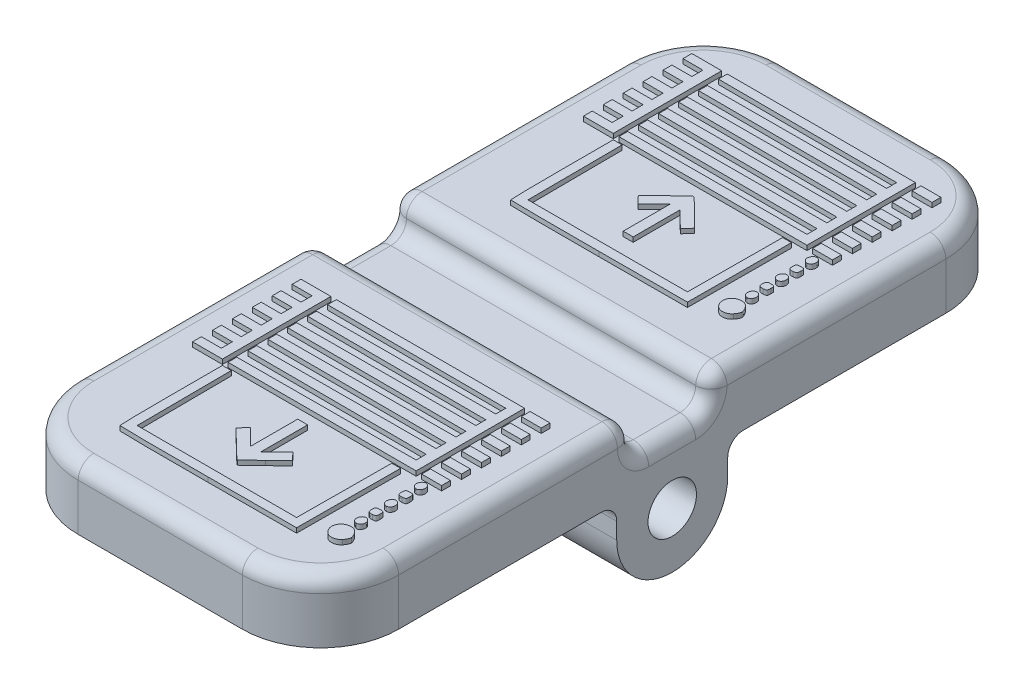
SolidWorks part; units mm, degrees
other "Camera1"
ref_plane "Front Plane" through (0, 0, 0) normal (0, 0, 1) x (1, 0, 0)
ref_plane "Top Plane" through (0, 0, 0) normal (0, 1, 0) x (1, 0, 0)
ref_plane "Right Plane" through (0, 0, 0) normal (1, 0, 0) x (0, 0, -1)
sketch "Sketch1" plane through (0, 0, 0) normal (0, 1, 0) x (1, 0, 0)
  line L1 (0, 0) -> (20.5, 0)
  line L2 (0, 0) -> (0, 45)
  line L3 (0, 45) -> (20.5, 45)
  line L4 (20.5, 0) -> (20.5, 45)
  dimension "D1" = 20.5
  dimension "D2" = 45
extrude "Boss-Extrude1" add sketch "Sketch1" along normal blind 2.5
sketch "Sketch2" plane through (0, 2.5, 0) normal (0, 1, 0) x (1, 0, 0)
  line L0 (20.5, 0) -> (20.5, 45) construction
  line L1 (0, 45) -> (20.5, 45)
  line L2 (0, 45) -> (0, 25)
  line L3 (0, 25) -> (20.5, 25)
  line L4 (20.5, 45) -> (20.5, 25)
  line L7 (0, 0) -> (20.5, 0)
  line L8 (0, 0) -> (0, 20)
  line L9 (0, 20) -> (20.5, 20)
  line L10 (20.5, 0) -> (20.5, 20)
  dimension "D1" = 20
  dimension "D2" = 20
extrude "Boss-Extrude2" add sketch "Sketch2" along normal blind 2
fillet "Fillet1" radius 1 16 edges at (0, 2.5, -22.5) (20.5, 2.5, -22.5) (10.25, 2.5, -20) (0, 4.5, -10) (10.25, 4.5, 0) (20.5, 4.5, -10) (10.25, 4.5, -20) (10.25, 2.5, -25) (10.25, 4.5, -25) (20.5, 4.5, -35) (10.25, 4.5, -45) (0, 4.5, -35) (0, 3.5, -20) (20.5, 3.5, -20) (20.5, 3.5, -25) (0, 3.5, -25)
fillet "Fillet2" radius 5 8 edges at (0.2929, 4.2071, -44.7071) (20.2071, 4.2071, -44.7071) (20.2071, 4.2071, -0.2929) (0.2929, 4.2071, -0.2929) (0, 1.75, 0) (20.5, 1.75, 0) (20.5, 1.75, -45) (0, 1.75, -45)
sketch "Sketch4" plane through (0, 0, 0) normal (-1, 0, 0) x (0, 0, 1)
  line L0 (-26.05, -1.55) -> (-26.05, 1.5)
  line L1 (-40, 0) -> (-5, 0) construction
  line L2 (-26.05, 1.5) -> (-18.95, 1.5)
  line L3 (-18.95, 1.5) -> (-18.95, -1.55)
  line L4 (-21, 1.5) -> (-24, 1.5) construction
  circle A0 centre (-22.5, -1.55) radius 1.55
  arc A1 (-26.05, -1.55) -> (-18.95, -1.55) centre (-22.5, -1.55) ccw
  circle A2 centre (-22.5, -1.55) radius 3.55 construction
  point P4 (-22.5, 0)
  dimension "D1" = 3.1
  dimension "D2" = 2
extrude "Boss-Extrude3" add sketch "Sketch4" against normal up to surface (20.5 mm away) up to face at (20.5, 2.0214, -22.5)
sketch "Sketch10" plane through (0, 0, 0) normal (0, -1, 0) x (1, 0, 0)
  line L8 (0, -18.95) -> (20.5, -18.95)
  line L9 (20.5, -18.95) -> (20.5, -5)
  line L10 (15.5, 0) -> (5, 0)
  line L11 (0, -5) -> (0, -18.95)
  line L16 (0, -18.95) -> (20.5, -18.95)
  line L17 (20.5, -18.95) -> (20.5, -5)
  line L18 (15.5, 0) -> (5, 0)
  line L19 (0, -5) -> (0, -18.95)
  line L24 (20.5, -26.05) -> (0, -26.05)
  line L25 (0, -26.05) -> (0, -40)
  line L26 (5, -45) -> (15.5, -45)
  line L27 (20.5, -40) -> (20.5, -26.05)
  line L28 (20.5, -26.05) -> (0, -26.05)
  line L29 (0, -26.05) -> (0, -40)
  line L30 (5, -45) -> (15.5, -45)
  line L31 (20.5, -40) -> (20.5, -26.05)
  arc A4 (20.5, -5) -> (15.5, 0) centre (15.5, -5) ccw
  arc A5 (5, 0) -> (0, -5) centre (5, -5) ccw
  arc A8 (20.5, -5) -> (15.5, 0) centre (15.5, -5) ccw
  arc A9 (5, 0) -> (0, -5) centre (5, -5) ccw
  arc A12 (0, -40) -> (5, -45) centre (5, -40) ccw
  arc A13 (15.5, -45) -> (20.5, -40) centre (15.5, -40) ccw
  arc A14 (0, -40) -> (5, -45) centre (5, -40) ccw
  arc A15 (15.5, -45) -> (20.5, -40) centre (15.5, -40) ccw
  dimension "D1" = 0
  dimension "D2" = 0
extrude "Cut-Extrude1" cut sketch "Sketch10" against normal blind 0.5
fillet "Fillet3" radius 1 2 edges at (10.25, 0.5, -18.95) (10.25, 0.5, -26.05)
sketch "Sketch8" plane through (0, 4.5, 0) normal (0, 1, 0) x (1, 0, 0)
  line L0 (4.5509, 31.3961) -> (4.5509, 34.6763)
  line L1 (4.5509, 34.6763) -> (4.8333, 34.6763)
  line L2 (4.8333, 34.6763) -> (5.1157, 34.6763)
  line L3 (5.1157, 34.6763) -> (5.1342, 31.6497)
  line L4 (5.1342, 31.6497) -> (5.1527, 28.6232)
  line L5 (5.1527, 28.6232) -> (10.25, 28.6232)
  line L6 (10.25, 28.6232) -> (15.3474, 28.6232)
  line L7 (15.3474, 28.6232) -> (15.3658, 31.6497)
  line L8 (15.3658, 31.6497) -> (15.3843, 34.6763)
  line L9 (15.3843, 34.6763) -> (15.6674, 34.6763)
  line L10 (15.6674, 34.6763) -> (15.9505, 34.6763)
  line L11 (15.9505, 34.6763) -> (15.9321, 31.3666)
  line L12 (15.9321, 31.3666) -> (15.9137, 28.0568)
  line L13 (15.9137, 28.0568) -> (10.2799, 28.0388)
  line L14 (9.9314, 31.4356) -> (9.9314, 32.9383)
  line L15 (9.9314, 32.9383) -> (9.4154, 32.4257)
  line L16 (9.4154, 32.4257) -> (8.8994, 31.9131)
  line L17 (8.8994, 31.9131) -> (8.6732, 32.1464)
  line L18 (8.6732, 32.1464) -> (8.447, 32.3798)
  line L19 (8.447, 32.3798) -> (9.3141, 33.2449)
  line L20 (11.1859, 33.2449) -> (12.053, 32.3798)
  line L21 (12.053, 32.3798) -> (11.8268, 32.1464)
  line L22 (11.8268, 32.1464) -> (11.6006, 31.9131)
  line L23 (11.6006, 31.9131) -> (11.0846, 32.4257)
  line L24 (11.0846, 32.4257) -> (10.5686, 32.9382)
  line L25 (10.5686, 32.9382) -> (10.5686, 31.4356)
  line L26 (10.5686, 31.4356) -> (10.5686, 29.9329)
  line L27 (10.5686, 29.9329) -> (10.25, 29.9329)
  line L28 (10.25, 29.9329) -> (9.9314, 29.9329)
  line L29 (9.9314, 29.9329) -> (9.9314, 31.4356)
  line L30 (2.2854, 35.3135) -> (2.2854, 35.5967)
  line L31 (2.2854, 35.5967) -> (2.9226, 35.5967)
  line L32 (2.9226, 35.5967) -> (3.5597, 35.5967)
  line L33 (3.5597, 35.5967) -> (3.5597, 35.9506)
  line L34 (3.5597, 35.9506) -> (3.5597, 36.3046)
  line L35 (3.5597, 36.3046) -> (2.9226, 36.3046)
  line L36 (2.9226, 36.3046) -> (2.2854, 36.3046)
  line L37 (2.2854, 36.3046) -> (2.2854, 36.5878)
  line L38 (2.2854, 36.5878) -> (2.2854, 36.871)
  line L39 (2.2854, 36.871) -> (2.9226, 36.871)
  line L40 (2.9226, 36.871) -> (3.5597, 36.871)
  line L41 (3.5597, 36.871) -> (3.5597, 37.225)
  line L42 (3.5597, 37.225) -> (3.5597, 37.579)
  line L43 (3.5597, 37.579) -> (2.9226, 37.579)
  line L44 (2.9226, 37.579) -> (2.2854, 37.579)
  line L45 (2.2854, 37.579) -> (2.2854, 37.8622)
  line L46 (2.2854, 37.8622) -> (2.2854, 38.1453)
  line L47 (2.2854, 38.1453) -> (2.9226, 38.1453)
  line L48 (2.9226, 38.1453) -> (3.5597, 38.1453)
  line L49 (3.5597, 38.1453) -> (3.5597, 38.4993)
  line L50 (3.5597, 38.4993) -> (3.5597, 38.8533)
  line L51 (3.5597, 38.8533) -> (2.9226, 38.8533)
  line L52 (2.9226, 38.8533) -> (2.2854, 38.8533)
  line L53 (2.2854, 38.8533) -> (2.2854, 39.1365)
  line L54 (2.2854, 39.1365) -> (2.2854, 39.4197)
  line L55 (2.2854, 39.4197) -> (2.9226, 39.4197)
  line L56 (2.9226, 39.4197) -> (3.5597, 39.4197)
  line L57 (3.5597, 39.4197) -> (3.5597, 39.7737)
  line L58 (3.5597, 39.7737) -> (3.5597, 40.1276)
  line L59 (3.5597, 40.1276) -> (2.9226, 40.1276)
  line L60 (2.9226, 40.1276) -> (2.2854, 40.1276)
  line L61 (2.2854, 40.1276) -> (2.2854, 40.4108)
  line L62 (2.2854, 40.4108) -> (2.2854, 40.694)
  line L63 (2.2854, 40.694) -> (2.9226, 40.694)
  line L64 (2.9226, 40.694) -> (3.5597, 40.694)
  line L65 (3.5597, 40.694) -> (3.5597, 41.048)
  line L66 (3.5597, 41.048) -> (3.5597, 41.402)
  line L67 (3.5597, 41.402) -> (2.9226, 41.402)
  line L68 (2.9226, 41.402) -> (2.2854, 41.402)
  line L69 (2.2854, 41.402) -> (2.2854, 41.6851)
  line L70 (2.2854, 41.6851) -> (2.2854, 41.9683)
  line L71 (2.2854, 41.9683) -> (3.2411, 41.9683)
  line L72 (3.2411, 41.9683) -> (4.1969, 41.9683)
  line L73 (4.1969, 41.9683) -> (4.1969, 38.4993)
  line L74 (4.1969, 38.4993) -> (4.1969, 35.0303)
  line L75 (4.1969, 35.0303) -> (3.2411, 35.0303)
  line L76 (3.2411, 35.0303) -> (2.2854, 35.0303)
  line L77 (2.2854, 35.0303) -> (2.2854, 35.3135)
  line L78 (4.5509, 35.3131) -> (4.5509, 35.5958)
  line L79 (4.5509, 35.5958) -> (10.2677, 35.614)
  line L80 (10.2677, 35.614) -> (15.9845, 35.6322)
  line L81 (15.9845, 35.6322) -> (15.9845, 35.9509)
  line L82 (15.9845, 35.9509) -> (15.9845, 36.2695)
  line L83 (15.9845, 36.2695) -> (10.2677, 36.2875)
  line L84 (10.2677, 36.2875) -> (4.5509, 36.3055)
  line L85 (4.5509, 36.3055) -> (4.5509, 36.5878)
  line L86 (4.5509, 36.5878) -> (4.5509, 36.8702)
  line L87 (4.5509, 36.8702) -> (10.2677, 36.8881)
  line L88 (10.2677, 36.8881) -> (15.9845, 36.9061)
  line L89 (15.9845, 36.9061) -> (15.9845, 37.2246)
  line L90 (15.9845, 37.2246) -> (15.9845, 37.5432)
  line L91 (15.9845, 37.5432) -> (10.2677, 37.5615)
  line L92 (10.2677, 37.5615) -> (4.5509, 37.5799)
  line L93 (4.5509, 37.5799) -> (4.5509, 37.8622)
  line L94 (4.5509, 37.8622) -> (4.5509, 38.1445)
  line L95 (4.5509, 38.1445) -> (10.2677, 38.1627)
  line L96 (10.2677, 38.1627) -> (15.9845, 38.181)
  line L97 (15.9845, 38.181) -> (15.9845, 38.4997)
  line L98 (15.9845, 38.4997) -> (15.9845, 38.8183)
  line L99 (15.9845, 38.8183) -> (10.2677, 38.8362)
  line L100 (10.2677, 38.8362) -> (4.5509, 38.854)
  line L101 (4.5509, 38.854) -> (4.5509, 39.1365)
  line L102 (4.5509, 39.1365) -> (4.5509, 39.4188)
  line L103 (4.5509, 39.4188) -> (10.2677, 39.4371)
  line L104 (10.2677, 39.4371) -> (15.9845, 39.4553)
  line L105 (15.9845, 39.4553) -> (15.9845, 39.774)
  line L106 (15.9845, 39.774) -> (15.9845, 40.0926)
  line L107 (15.9845, 40.0926) -> (10.2677, 40.1106)
  line L108 (10.2677, 40.1106) -> (4.5509, 40.1286)
  line L109 (4.5509, 40.1286) -> (4.5509, 40.4108)
  line L110 (4.5509, 40.4108) -> (4.5509, 40.6932)
  line L111 (4.5509, 40.6932) -> (10.2677, 40.711)
  line L112 (10.2677, 40.711) -> (15.9845, 40.7289)
  line L113 (15.9845, 40.7289) -> (15.9845, 41.0476)
  line L114 (15.9845, 41.0476) -> (15.9845, 41.3662)
  line L115 (15.9845, 41.3662) -> (10.2677, 41.3846)
  line L116 (10.2677, 41.3846) -> (4.5509, 41.4029)
  line L117 (4.5509, 41.4029) -> (4.5509, 41.6856)
  line L118 (4.5509, 41.6856) -> (4.5509, 41.9683)
  line L119 (4.5509, 41.9683) -> (10.5686, 41.9683)
  line L120 (10.5686, 41.9683) -> (16.5863, 41.9683)
  line L121 (16.5863, 41.9683) -> (16.5863, 38.4993)
  line L122 (16.5863, 38.4993) -> (16.5863, 35.0303)
  line L123 (16.5863, 35.0303) -> (10.5686, 35.0303)
  line L124 (10.5686, 35.0303) -> (4.5509, 35.0303)
  line L125 (4.5509, 35.0303) -> (4.5509, 35.3131)
  line L126 (16.9403, 35.3135) -> (16.9403, 35.5967)
  line L127 (16.9403, 35.5967) -> (17.5774, 35.5967)
  line L128 (17.5774, 35.5967) -> (18.2146, 35.5967)
  line L129 (18.2146, 35.5967) -> (18.2146, 35.3135)
  line L130 (18.2146, 35.3135) -> (18.2146, 35.0303)
  line L131 (18.2146, 35.0303) -> (17.5774, 35.0303)
  line L132 (17.5774, 35.0303) -> (16.9403, 35.0303)
  line L133 (16.9403, 35.0303) -> (16.9403, 35.3135)
  line L134 (16.9403, 36.5878) -> (16.9403, 36.871)
  line L135 (16.9403, 36.871) -> (17.5774, 36.871)
  line L136 (17.5774, 36.871) -> (18.2146, 36.871)
  line L137 (18.2146, 36.871) -> (18.2146, 36.5878)
  line L138 (18.2146, 36.5878) -> (18.2146, 36.3046)
  line L139 (18.2146, 36.3046) -> (17.5774, 36.3046)
  line L140 (17.5774, 36.3046) -> (16.9403, 36.3046)
  line L141 (16.9403, 36.3046) -> (16.9403, 36.5878)
  line L142 (16.9403, 37.8622) -> (16.9403, 38.1453)
  line L143 (16.9403, 38.1453) -> (17.5774, 38.1453)
  line L144 (17.5774, 38.1453) -> (18.2146, 38.1453)
  line L145 (18.2146, 38.1453) -> (18.2146, 37.8622)
  line L146 (18.2146, 37.8622) -> (18.2146, 37.579)
  line L147 (18.2146, 37.579) -> (17.5774, 37.579)
  line L148 (17.5774, 37.579) -> (16.9403, 37.579)
  line L149 (16.9403, 37.579) -> (16.9403, 37.8622)
  line L150 (16.9403, 39.1365) -> (16.9403, 39.4197)
  line L151 (16.9403, 39.4197) -> (17.5774, 39.4197)
  line L152 (17.5774, 39.4197) -> (18.2146, 39.4197)
  line L153 (18.2146, 39.4197) -> (18.2146, 39.1365)
  line L154 (18.2146, 39.1365) -> (18.2146, 38.8533)
  line L155 (18.2146, 38.8533) -> (17.5774, 38.8533)
  line L156 (17.5774, 38.8533) -> (16.9403, 38.8533)
  line L157 (16.9403, 38.8533) -> (16.9403, 39.1365)
  line L158 (16.9403, 40.4108) -> (16.9403, 40.694)
  line L159 (16.9403, 40.694) -> (17.5774, 40.694)
  line L160 (17.5774, 40.694) -> (18.2146, 40.694)
  line L161 (18.2146, 40.694) -> (18.2146, 40.4108)
  line L162 (18.2146, 40.4108) -> (18.2146, 40.1276)
  line L163 (18.2146, 40.1276) -> (17.5774, 40.1276)
  line L164 (17.5774, 40.1276) -> (16.9403, 40.1276)
  line L165 (16.9403, 40.1276) -> (16.9403, 40.4108)
  line L166 (16.9403, 41.6851) -> (16.9403, 41.9683)
  line L167 (16.9403, 41.9683) -> (17.5774, 41.9683)
  line L168 (17.5774, 41.9683) -> (18.2146, 41.9683)
  line L169 (18.2146, 41.9683) -> (18.2146, 41.6851)
  line L170 (18.2146, 41.6851) -> (18.2146, 41.402)
  line L171 (18.2146, 41.402) -> (17.5774, 41.402)
  line L172 (17.5774, 41.402) -> (16.9403, 41.402)
  line L173 (16.9403, 41.402) -> (16.9403, 41.6851)
  spline S0 degree 3 poles (4.5985, 28.0682) (4.5723, 28.0944) (4.5509, 29.5919) (4.5509, 31.3961) knots 0 0 0 0 1 1 1 1
  spline S1 degree 3 poles (10.2799, 28.0388) (7.1813, 28.0287) (4.6247, 28.0419) (4.5985, 28.0682) knots 0 0 0 0 1 1 1 1
  spline S2 degree 3 poles (17.1669, 28.8022) (16.7381, 29.2016) (16.9983, 29.8621) (17.5845, 29.8621) knots 0 0 0 0 1 1 1 1
  spline S3 degree 3 poles (17.5845, 29.8621) (17.7919, 29.8621) (17.8871, 29.8157) (18.0313, 29.6443) knots 0 0 0 0 1 1 1 1
  spline S4 degree 3 poles (18.0313, 29.6443) (18.1321, 29.5245) (18.2146, 29.3518) (18.2146, 29.2604) knots 0 0 0 0 1 1 1 1
  spline S5 degree 3 poles (18.2146, 29.2604) (18.2146, 29.169) (18.1321, 28.9962) (18.0313, 28.8764) knots 0 0 0 0 1 1 1 1
  spline S6 degree 3 poles (18.0313, 28.8764) (17.8058, 28.6085) (17.4112, 28.5745) (17.1669, 28.8022) knots 0 0 0 0 1 1 1 1
  spline S7 degree 3 poles (9.3141, 33.2449) (9.791, 33.7207) (10.2122, 34.1099) (10.25, 34.1099) knots 0 0 0 0 1 1 1 1
  spline S8 degree 3 poles (10.25, 34.1099) (10.2878, 34.1099) (10.709, 33.7207) (11.1859, 33.2449) knots 0 0 0 0 1 1 1 1
  spline S9 degree 3 poles (17.3683, 30.3184) (17.1669, 30.5611) (17.4446, 30.9712) (17.7013, 30.8103) knots 0 0 0 0 1 1 1 1
  spline S10 degree 3 poles (17.7013, 30.8103) (17.954, 30.6519) (17.8631, 30.2161) (17.5774, 30.2161) knots 0 0 0 0 1 1 1 1
  spline S11 degree 3 poles (17.5774, 30.2161) (17.5091, 30.2161) (17.415, 30.2622) (17.3683, 30.3184) knots 0 0 0 0 1 1 1 1
  spline S12 degree 3 poles (17.3236, 31.3038) (17.3013, 31.3619) (17.2935, 31.4834) (17.3064, 31.5738) knots 0 0 0 0 1 1 1 1
  spline S13 degree 3 poles (17.3064, 31.5738) (17.3257, 31.7101) (17.3721, 31.7382) (17.5774, 31.7382) knots 0 0 0 0 1 1 1 1
  spline S14 degree 3 poles (17.5774, 31.7382) (17.8134, 31.7382) (17.8252, 31.7263) (17.8252, 31.4905) knots 0 0 0 0 1 1 1 1
  spline S15 degree 3 poles (17.8252, 31.4905) (17.8252, 31.2625) (17.8067, 31.2409) (17.5946, 31.2205) knots 0 0 0 0 1 1 1 1
  spline S16 degree 3 poles (17.5946, 31.2205) (17.44, 31.2056) (17.3507, 31.2329) (17.3236, 31.3038) knots 0 0 0 0 1 1 1 1
  spline S17 degree 3 poles (17.3683, 32.2299) (17.1669, 32.4726) (17.4446, 32.8827) (17.7013, 32.7218) knots 0 0 0 0 1 1 1 1
  spline S18 degree 3 poles (17.7013, 32.7218) (17.954, 32.5635) (17.8631, 32.1276) (17.5774, 32.1276) knots 0 0 0 0 1 1 1 1
  spline S19 degree 3 poles (17.5774, 32.1276) (17.5091, 32.1276) (17.415, 32.1737) (17.3683, 32.2299) knots 0 0 0 0 1 1 1 1
  spline S20 degree 3 poles (17.3236, 33.2153) (17.3013, 33.2734) (17.2935, 33.3949) (17.3064, 33.4853) knots 0 0 0 0 1 1 1 1
  spline S21 degree 3 poles (17.3064, 33.4853) (17.3257, 33.6216) (17.3721, 33.6497) (17.5774, 33.6497) knots 0 0 0 0 1 1 1 1
  spline S22 degree 3 poles (17.5774, 33.6497) (17.8134, 33.6497) (17.8252, 33.6378) (17.8252, 33.402) knots 0 0 0 0 1 1 1 1
  spline S23 degree 3 poles (17.8252, 33.402) (17.8252, 33.1741) (17.8067, 33.1524) (17.5946, 33.132) knots 0 0 0 0 1 1 1 1
  spline S24 degree 3 poles (17.5946, 33.132) (17.44, 33.1171) (17.3507, 33.1444) (17.3236, 33.2153) knots 0 0 0 0 1 1 1 1
  spline S25 degree 3 poles (17.3683, 34.1414) (17.1669, 34.3841) (17.4446, 34.7942) (17.7013, 34.6333) knots 0 0 0 0 1 1 1 1
  spline S26 degree 3 poles (17.7013, 34.6333) (17.954, 34.475) (17.8631, 34.0391) (17.5774, 34.0391) knots 0 0 0 0 1 1 1 1
  spline S27 degree 3 poles (17.5774, 34.0391) (17.5091, 34.0391) (17.415, 34.0852) (17.3683, 34.1414) knots 0 0 0 0 1 1 1 1
extrude "Boss-Extrude4" add sketch "Sketch8" along normal blind 0.3 contours L77 L76 L75 L74 L73 L72 L71 L70 L69 L68 L67 L66 L65 L64 L63 L62 L61 L60 L59 L58 L57 L56 L55 L54 L53 L52 L51 L50 L49 L48 L47 L46 L45 L44 L43 L42 L41 L40 L39 L38 L37 L36 L35 L34 L33 L32 L31 L30 | L125 L124 L123 L122 L121 L120 L119 L118 L117 L116 L115 L114 L113 L112 L111 L110 L109 L108 L107 L106 L105 L104 L103 L102 L101 L100 L99 L98 L97 L96 L95 L94 L93 L92 L91 L90 L89 L88 L87 L86 L85 L84 L83 L82 L81 L80 L79 L78 | L173 L172 L171 L170 L169 L168 L167 L166 | L165 L164 L163 L162 L161 L160 L159 L158 | L157 L156 L155 L154 L153 L152 L151 L150 | L149 L148 L147 L146 L145 L144 L143 L142 | L141 L140 L139 L138 L137 L136 L135 L134 | L133 L132 L131 L130 L129 L128 L127 L126 | S27 S26 S25 | S8 S7 L19 L18 L17 L16 L15 L14 L29 L28 L27 L26 L25 L24 L23 L22 L21 L20 | S24 S23 S22 S21 S20 | S19 S18 S17 | S16 S15 S14 S13 S12 | S11 S10 S9 | S6 S5 S4 S3 S2 | S0 L0 L1 L2 L3 L4 L5 L6 L7 L8 L9 L10 L11 L12 L13 S1 region at (10.25, 4.5, -32.352) region at (2.3574, 4.5, -35.4551) region at (4.6898, 4.5, -35.4544) region at (17.5774, 4.5, -35.3135) region at (17.5774, 4.5, -36.5878) region at (17.5774, 4.5, -37.8622) region at (17.5774, 4.5, -39.1365) region at (17.5774, 4.5, -40.4108) region at (17.5774, 4.5, -41.6851) region at (17.5709, 4.5, -29.2604) region at (17.5762, 4.5, -30.5286) region at (17.5655, 4.5, -31.4805) region at (17.5762, 4.5, -32.4401) region at (17.5655, 4.5, -33.392) region at (17.5762, 4.5, -34.3516)
sketch "Sketch9" plane through (0, 4.5, 0) normal (0, 1, 0) x (1, 0, 0)
  line L0 (4.5509, 6.3961) -> (4.5509, 9.6763)
  line L1 (4.5509, 9.6763) -> (4.8333, 9.6763)
  line L2 (4.8333, 9.6763) -> (5.1157, 9.6763)
  line L3 (5.1157, 9.6763) -> (5.1342, 6.6498)
  line L4 (5.1342, 6.6498) -> (5.1527, 3.6232)
  line L5 (5.1527, 3.6232) -> (10.25, 3.6232)
  line L6 (10.25, 3.6232) -> (15.3474, 3.6232)
  line L7 (15.3474, 3.6232) -> (15.3658, 6.6498)
  line L8 (15.3658, 6.6498) -> (15.3843, 9.6763)
  line L9 (15.3843, 9.6763) -> (15.6674, 9.6763)
  line L10 (15.6674, 9.6763) -> (15.9505, 9.6763)
  line L11 (15.9505, 9.6763) -> (15.9321, 6.366)
  line L12 (15.9321, 6.366) -> (15.9137, 3.0562)
  line L13 (15.9137, 3.0562) -> (10.2799, 3.0382)
  line L14 (10.5686, 7.6073) -> (10.5686, 6.1046)
  line L15 (10.5686, 6.1046) -> (11.0846, 6.6172)
  line L16 (11.0846, 6.6172) -> (11.6006, 7.1298)
  line L17 (11.6006, 7.1298) -> (11.8268, 6.8964)
  line L18 (11.8268, 6.8964) -> (12.053, 6.6631)
  line L19 (12.053, 6.6631) -> (11.1859, 5.798)
  line L20 (9.3141, 5.798) -> (8.447, 6.6631)
  line L21 (8.447, 6.6631) -> (8.6732, 6.8964)
  line L22 (8.6732, 6.8964) -> (8.8994, 7.1298)
  line L23 (8.8994, 7.1298) -> (9.4154, 6.6172)
  line L24 (9.4154, 6.6172) -> (9.9314, 6.1046)
  line L25 (9.9314, 6.1046) -> (9.9314, 7.6073)
  line L26 (9.9314, 7.6073) -> (9.9314, 9.1099)
  line L27 (9.9314, 9.1099) -> (10.25, 9.1099)
  line L28 (10.25, 9.1099) -> (10.5686, 9.1099)
  line L29 (10.5686, 9.1099) -> (10.5686, 7.6073)
  line L30 (2.2854, 10.3135) -> (2.2854, 10.5967)
  line L31 (2.2854, 10.5967) -> (2.9226, 10.5967)
  line L32 (2.9226, 10.5967) -> (3.5597, 10.5967)
  line L33 (3.5597, 10.5967) -> (3.5597, 10.9506)
  line L34 (3.5597, 10.9506) -> (3.5597, 11.3046)
  line L35 (3.5597, 11.3046) -> (2.9226, 11.3046)
  line L36 (2.9226, 11.3046) -> (2.2854, 11.3046)
  line L37 (2.2854, 11.3046) -> (2.2854, 11.5878)
  line L38 (2.2854, 11.5878) -> (2.2854, 11.871)
  line L39 (2.2854, 11.871) -> (2.9226, 11.871)
  line L40 (2.9226, 11.871) -> (3.5597, 11.871)
  line L41 (3.5597, 11.871) -> (3.5597, 12.225)
  line L42 (3.5597, 12.225) -> (3.5597, 12.579)
  line L43 (3.5597, 12.579) -> (2.9226, 12.579)
  line L44 (2.9226, 12.579) -> (2.2854, 12.579)
  line L45 (2.2854, 12.579) -> (2.2854, 12.8622)
  line L46 (2.2854, 12.8622) -> (2.2854, 13.1453)
  line L47 (2.2854, 13.1453) -> (2.9226, 13.1453)
  line L48 (2.9226, 13.1453) -> (3.5597, 13.1453)
  line L49 (3.5597, 13.1453) -> (3.5597, 13.4993)
  line L50 (3.5597, 13.4993) -> (3.5597, 13.8533)
  line L51 (3.5597, 13.8533) -> (2.9226, 13.8533)
  line L52 (2.9226, 13.8533) -> (2.2854, 13.8533)
  line L53 (2.2854, 13.8533) -> (2.2854, 14.1365)
  line L54 (2.2854, 14.1365) -> (2.2854, 14.4197)
  line L55 (2.2854, 14.4197) -> (2.9226, 14.4197)
  line L56 (2.9226, 14.4197) -> (3.5597, 14.4197)
  line L57 (3.5597, 14.4197) -> (3.5597, 14.7737)
  line L58 (3.5597, 14.7737) -> (3.5597, 15.1276)
  line L59 (3.5597, 15.1276) -> (2.9226, 15.1276)
  line L60 (2.9226, 15.1276) -> (2.2854, 15.1276)
  line L61 (2.2854, 15.1276) -> (2.2854, 15.4108)
  line L62 (2.2854, 15.4108) -> (2.2854, 15.694)
  line L63 (2.2854, 15.694) -> (2.9226, 15.694)
  line L64 (2.9226, 15.694) -> (3.5597, 15.694)
  line L65 (3.5597, 15.694) -> (3.5597, 16.048)
  line L66 (3.5597, 16.048) -> (3.5597, 16.402)
  line L67 (3.5597, 16.402) -> (2.9226, 16.402)
  line L68 (2.9226, 16.402) -> (2.2854, 16.402)
  line L69 (2.2854, 16.402) -> (2.2854, 16.6851)
  line L70 (2.2854, 16.6851) -> (2.2854, 16.9683)
  line L71 (2.2854, 16.9683) -> (3.2412, 16.9683)
  line L72 (3.2412, 16.9683) -> (4.1969, 16.9683)
  line L73 (4.1969, 16.9683) -> (4.1969, 13.4993)
  line L74 (4.1969, 13.4993) -> (4.1969, 10.0303)
  line L75 (4.1969, 10.0303) -> (3.2412, 10.0303)
  line L76 (3.2412, 10.0303) -> (2.2854, 10.0303)
  line L77 (2.2854, 10.0303) -> (2.2854, 10.3135)
  line L78 (4.5509, 10.3131) -> (4.5509, 10.5958)
  line L79 (4.5509, 10.5958) -> (10.2677, 10.6139)
  line L80 (10.2677, 10.6139) -> (15.9845, 10.6319)
  line L81 (15.9845, 10.6319) -> (15.9845, 10.9506)
  line L82 (15.9845, 10.9506) -> (15.9845, 11.2692)
  line L83 (15.9845, 11.2692) -> (10.2677, 11.2873)
  line L84 (10.2677, 11.2873) -> (4.5509, 11.3053)
  line L85 (4.5509, 11.3053) -> (4.5509, 11.5878)
  line L86 (4.5509, 11.5878) -> (4.5509, 11.8702)
  line L87 (4.5509, 11.8702) -> (10.2677, 11.8882)
  line L88 (10.2677, 11.8882) -> (15.9845, 11.9062)
  line L89 (15.9845, 11.9062) -> (15.9845, 12.2252)
  line L90 (15.9845, 12.2252) -> (15.9845, 12.5438)
  line L91 (15.9845, 12.5438) -> (10.2677, 12.5619)
  line L92 (10.2677, 12.5619) -> (4.5509, 12.5799)
  line L93 (4.5509, 12.5799) -> (4.5509, 12.8622)
  line L94 (4.5509, 12.8622) -> (4.5509, 13.1445)
  line L95 (4.5509, 13.1445) -> (10.2677, 13.1626)
  line L96 (10.2677, 13.1626) -> (15.9845, 13.1806)
  line L97 (15.9845, 13.1806) -> (15.9845, 13.4993)
  line L98 (15.9845, 13.4993) -> (15.9845, 13.8179)
  line L99 (15.9845, 13.8179) -> (10.2677, 13.836)
  line L100 (10.2677, 13.836) -> (4.5509, 13.854)
  line L101 (4.5509, 13.854) -> (4.5509, 14.1365)
  line L102 (4.5509, 14.1365) -> (4.5509, 14.4189)
  line L103 (4.5509, 14.4189) -> (10.2677, 14.4369)
  line L104 (10.2677, 14.4369) -> (15.9845, 14.4549)
  line L105 (15.9845, 14.4549) -> (15.9845, 14.7736)
  line L106 (15.9845, 14.7736) -> (15.9845, 15.0922)
  line L107 (15.9845, 15.0922) -> (10.2677, 15.1103)
  line L108 (10.2677, 15.1103) -> (4.5509, 15.1283)
  line L109 (4.5509, 15.1283) -> (4.5509, 15.4107)
  line L110 (4.5509, 15.4107) -> (4.5509, 15.6932)
  line L111 (4.5509, 15.6932) -> (10.2677, 15.7112)
  line L112 (10.2677, 15.7112) -> (15.9845, 15.7293)
  line L113 (15.9845, 15.7293) -> (15.9845, 16.048)
  line L114 (15.9845, 16.048) -> (15.9845, 16.3666)
  line L115 (15.9845, 16.3666) -> (10.2677, 16.3846)
  line L116 (10.2677, 16.3846) -> (4.5509, 16.4027)
  line L117 (4.5509, 16.4027) -> (4.5509, 16.6856)
  line L118 (4.5509, 16.6856) -> (4.5509, 16.9683)
  line L119 (4.5509, 16.9683) -> (10.5686, 16.9683)
  line L120 (10.5686, 16.9683) -> (16.5863, 16.9683)
  line L121 (16.5863, 16.9683) -> (16.5863, 13.4993)
  line L122 (16.5863, 13.4993) -> (16.5863, 10.0303)
  line L123 (16.5863, 10.0303) -> (10.5686, 10.0303)
  line L124 (10.5686, 10.0303) -> (4.5509, 10.0303)
  line L125 (4.5509, 10.0303) -> (4.5509, 10.3131)
  line L126 (16.9403, 10.3135) -> (16.9403, 10.5967)
  line L127 (16.9403, 10.5967) -> (17.5774, 10.5967)
  line L128 (17.5774, 10.5967) -> (18.2146, 10.5967)
  line L129 (18.2146, 10.5967) -> (18.2146, 10.3135)
  line L130 (18.2146, 10.3135) -> (18.2146, 10.0303)
  line L131 (18.2146, 10.0303) -> (17.5774, 10.0303)
  line L132 (17.5774, 10.0303) -> (16.9403, 10.0303)
  line L133 (16.9403, 10.0303) -> (16.9403, 10.3135)
  line L134 (16.9403, 11.5878) -> (16.9403, 11.871)
  line L135 (16.9403, 11.871) -> (17.5774, 11.871)
  line L136 (17.5774, 11.871) -> (18.2146, 11.871)
  line L137 (18.2146, 11.871) -> (18.2146, 11.5878)
  line L138 (18.2146, 11.5878) -> (18.2146, 11.3046)
  line L139 (18.2146, 11.3046) -> (17.5774, 11.3046)
  line L140 (17.5774, 11.3046) -> (16.9403, 11.3046)
  line L141 (16.9403, 11.3046) -> (16.9403, 11.5878)
  line L142 (16.9403, 12.8622) -> (16.9403, 13.1453)
  line L143 (16.9403, 13.1453) -> (17.5774, 13.1453)
  line L144 (17.5774, 13.1453) -> (18.2146, 13.1453)
  line L145 (18.2146, 13.1453) -> (18.2146, 12.8622)
  line L146 (18.2146, 12.8622) -> (18.2146, 12.579)
  line L147 (18.2146, 12.579) -> (17.5774, 12.579)
  line L148 (17.5774, 12.579) -> (16.9403, 12.579)
  line L149 (16.9403, 12.579) -> (16.9403, 12.8622)
  line L150 (16.9403, 14.1365) -> (16.9403, 14.4197)
  line L151 (16.9403, 14.4197) -> (17.5774, 14.4197)
  line L152 (17.5774, 14.4197) -> (18.2146, 14.4197)
  line L153 (18.2146, 14.4197) -> (18.2146, 14.1365)
  line L154 (18.2146, 14.1365) -> (18.2146, 13.8533)
  line L155 (18.2146, 13.8533) -> (17.5774, 13.8533)
  line L156 (17.5774, 13.8533) -> (16.9403, 13.8533)
  line L157 (16.9403, 13.8533) -> (16.9403, 14.1365)
  line L158 (16.9403, 15.4108) -> (16.9403, 15.694)
  line L159 (16.9403, 15.694) -> (17.5774, 15.694)
  line L160 (17.5774, 15.694) -> (18.2146, 15.694)
  line L161 (18.2146, 15.694) -> (18.2146, 15.4108)
  line L162 (18.2146, 15.4108) -> (18.2146, 15.1276)
  line L163 (18.2146, 15.1276) -> (17.5774, 15.1276)
  line L164 (17.5774, 15.1276) -> (16.9403, 15.1276)
  line L165 (16.9403, 15.1276) -> (16.9403, 15.4108)
  line L166 (16.9403, 16.6851) -> (16.9403, 16.9683)
  line L167 (16.9403, 16.9683) -> (17.5774, 16.9683)
  line L168 (17.5774, 16.9683) -> (18.2146, 16.9683)
  line L169 (18.2146, 16.9683) -> (18.2146, 16.6851)
  line L170 (18.2146, 16.6851) -> (18.2146, 16.402)
  line L171 (18.2146, 16.402) -> (17.5774, 16.402)
  line L172 (17.5774, 16.402) -> (16.9403, 16.402)
  line L173 (16.9403, 16.402) -> (16.9403, 16.6851)
  spline S0 degree 3 poles (4.5985, 3.0682) (4.5723, 3.0944) (4.5509, 4.5919) (4.5509, 6.3961) knots 0 0 0 0 1 1 1 1
  spline S1 degree 3 poles (10.2799, 3.0382) (7.1813, 3.0284) (4.6247, 3.0419) (4.5985, 3.0682) knots 0 0 0 0 1 1 1 1
  spline S2 degree 3 poles (17.1669, 3.8022) (16.7381, 4.2016) (16.9983, 4.8621) (17.5845, 4.8621) knots 0 0 0 0 1 1 1 1
  spline S3 degree 3 poles (17.5845, 4.8621) (17.7919, 4.8621) (17.8871, 4.8157) (18.0313, 4.6443) knots 0 0 0 0 1 1 1 1
  spline S4 degree 3 poles (18.0313, 4.6443) (18.1321, 4.5245) (18.2146, 4.3518) (18.2146, 4.2604) knots 0 0 0 0 1 1 1 1
  spline S5 degree 3 poles (18.2146, 4.2604) (18.2146, 4.169) (18.1321, 3.9962) (18.0313, 3.8764) knots 0 0 0 0 1 1 1 1
  spline S6 degree 3 poles (18.0313, 3.8764) (17.8058, 3.6085) (17.4112, 3.5745) (17.1669, 3.8022) knots 0 0 0 0 1 1 1 1
  spline S7 degree 3 poles (11.1859, 5.798) (10.709, 5.3222) (10.2878, 4.9329) (10.25, 4.9329) knots 0 0 0 0 1 1 1 1
  spline S8 degree 3 poles (10.25, 4.9329) (10.2122, 4.9329) (9.791, 5.3222) (9.3141, 5.798) knots 0 0 0 0 1 1 1 1
  spline S9 degree 3 poles (17.3683, 5.3184) (17.1669, 5.5611) (17.4446, 5.9712) (17.7013, 5.8103) knots 0 0 0 0 1 1 1 1
  spline S10 degree 3 poles (17.7013, 5.8103) (17.954, 5.6519) (17.8631, 5.2161) (17.5774, 5.2161) knots 0 0 0 0 1 1 1 1
  spline S11 degree 3 poles (17.5774, 5.2161) (17.5091, 5.2161) (17.415, 5.2622) (17.3683, 5.3184) knots 0 0 0 0 1 1 1 1
  spline S12 degree 3 poles (17.3236, 6.3038) (17.3013, 6.3619) (17.2935, 6.4834) (17.3064, 6.5738) knots 0 0 0 0 1 1 1 1
  spline S13 degree 3 poles (17.3064, 6.5738) (17.3257, 6.7101) (17.3721, 6.7382) (17.5774, 6.7382) knots 0 0 0 0 1 1 1 1
  spline S14 degree 3 poles (17.5774, 6.7382) (17.8134, 6.7382) (17.8252, 6.7263) (17.8252, 6.4905) knots 0 0 0 0 1 1 1 1
  spline S15 degree 3 poles (17.8252, 6.4905) (17.8252, 6.2625) (17.8067, 6.2409) (17.5946, 6.2205) knots 0 0 0 0 1 1 1 1
  spline S16 degree 3 poles (17.5946, 6.2205) (17.44, 6.2056) (17.3507, 6.2329) (17.3236, 6.3038) knots 0 0 0 0 1 1 1 1
  spline S17 degree 3 poles (17.3683, 7.2299) (17.1669, 7.4726) (17.4446, 7.8827) (17.7013, 7.7218) knots 0 0 0 0 1 1 1 1
  spline S18 degree 3 poles (17.7013, 7.7218) (17.954, 7.5634) (17.8631, 7.1276) (17.5774, 7.1276) knots 0 0 0 0 1 1 1 1
  spline S19 degree 3 poles (17.5774, 7.1276) (17.5091, 7.1276) (17.415, 7.1737) (17.3683, 7.2299) knots 0 0 0 0 1 1 1 1
  spline S20 degree 3 poles (17.3236, 8.2153) (17.3013, 8.2734) (17.2935, 8.3949) (17.3064, 8.4853) knots 0 0 0 0 1 1 1 1
  spline S21 degree 3 poles (17.3064, 8.4853) (17.3257, 8.6216) (17.3721, 8.6498) (17.5774, 8.6498) knots 0 0 0 0 1 1 1 1
  spline S22 degree 3 poles (17.5774, 8.6498) (17.8134, 8.6497) (17.8252, 8.6378) (17.8252, 8.402) knots 0 0 0 0 1 1 1 1
  spline S23 degree 3 poles (17.8252, 8.402) (17.8252, 8.1741) (17.8067, 8.1524) (17.5946, 8.132) knots 0 0 0 0 1 1 1 1
  spline S24 degree 3 poles (17.5946, 8.132) (17.44, 8.1171) (17.3507, 8.1444) (17.3236, 8.2153) knots 0 0 0 0 1 1 1 1
  spline S25 degree 3 poles (17.3683, 9.1414) (17.1669, 9.3841) (17.4446, 9.7942) (17.7013, 9.6333) knots 0 0 0 0 1 1 1 1
  spline S26 degree 3 poles (17.7013, 9.6333) (17.954, 9.475) (17.8631, 9.0391) (17.5774, 9.0391) knots 0 0 0 0 1 1 1 1
  spline S27 degree 3 poles (17.5774, 9.0391) (17.5091, 9.0391) (17.415, 9.0852) (17.3683, 9.1414) knots 0 0 0 0 1 1 1 1
extrude "Boss-Extrude5" add sketch "Sketch9" along normal blind 0.3
ref_plane "ground" through (0, 0, 0) normal (0, -0.9702, 0.2421) x (-1, 0, 0)
equation "\"D2@Sketch2\"=\"D1@Sketch2\""
equation "\"icon_thickness\"=0.3"
equation "\"D1@Boss-Extrude4\"=\"icon_thickness\""
equation "\"D1@Boss-Extrude5\"=\"icon_thickness\""
